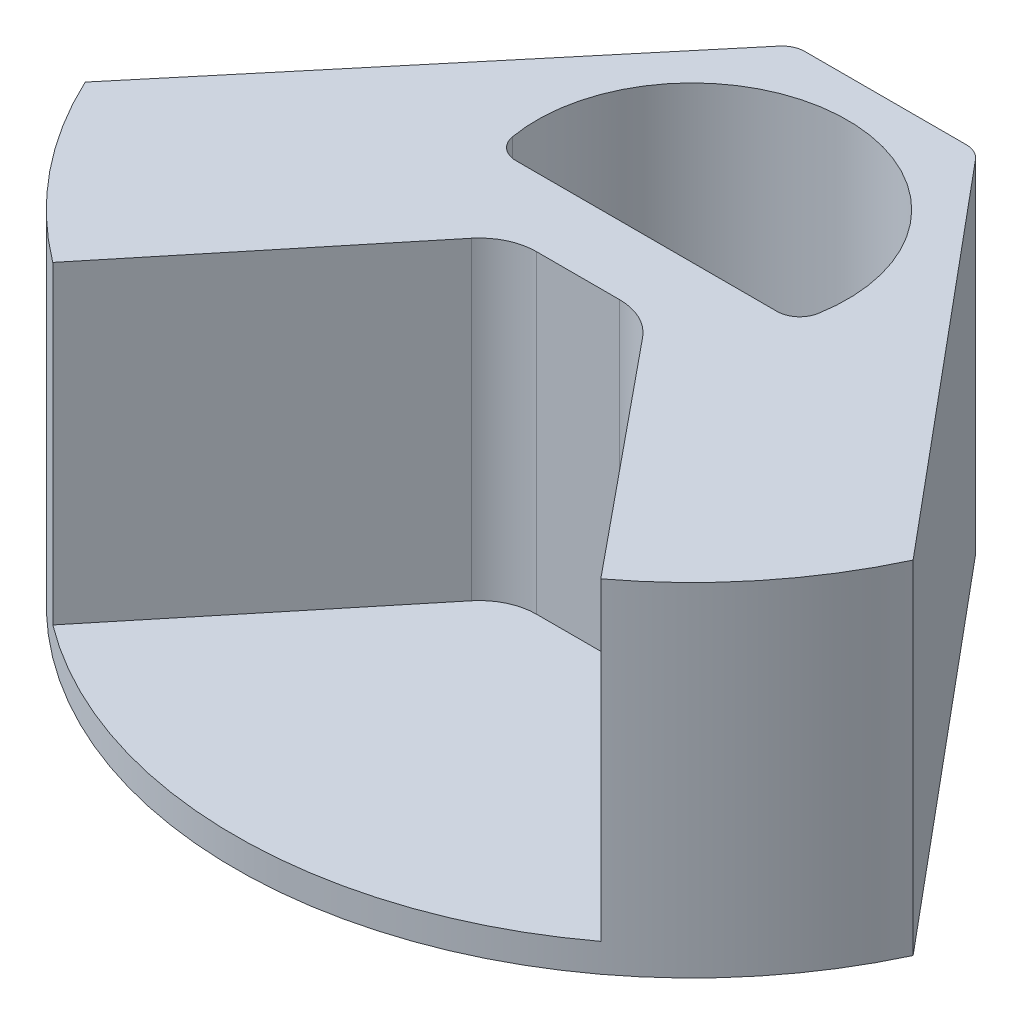
SolidWorks part; units mm, degrees
ref_plane "Front Plane" through (0, 0, 0) normal (0, 0, 1) x (1, 0, 0)
ref_plane "Top Plane" through (0, 0, 0) normal (0, 1, 0) x (1, 0, 0)
ref_plane "Right Plane" through (0, 0, 0) normal (1, 0, 0) x (0, 0, -1)
sketch "Sketch1" plane through (0, 0, 0) normal (0, 1, 0) x (1, 0, 0)
  circle A0 centre (0, 0) radius 50.8
  dimension "D1" = 101.6
extrude "Boss-Extrude1" add sketch "Sketch1" along normal blind 38.1
sketch "Sketch2" plane through (0, 38.1, 0) normal (0, 1, 0) x (1, 0, 0)
  line L0 (30.48, -40.64) -> (7.62, -12.7)
  line L1 (-7.62, -12.7) -> (7.62, -12.7)
  line L2 (-30.48, -40.64) -> (-30.48, -50.8)
  line L3 (-30.48, -50.8) -> (30.48, -50.8)
  line L4 (30.48, -40.64) -> (30.48, -50.8)
  line L5 (0, -20.955) -> (0, 20.955) construction
  line L6 (-30.48, -40.64) -> (-7.62, -12.7)
  circle A1 centre (0, 0) radius 50.8 construction
  dimension "D1" = 12.7
  dimension "D2" = 30.48
  dimension "D3" = 7.62
extrude "Cut-Extrude1" cut sketch "Sketch2" against normal offset from surface (34.925 mm away) 3.175 up to face at (0, 0, 50.8)
fillet "Fillet1" radius 6.35 2 edges at (7.62, 20.6375, 12.7) (-7.62, 20.6375, 12.7)
hole_wizard "M4 Clearance Hole1" positions "Sketch4" profile "Sketch5" hole size "M4" standard "ANSI Metric" end condition through all
sketch "Sketch4" plane through (0, 38.1, 0) normal (0, 1, 0) x (1, 0, 0)
  point P0 (0, 0)
sketch "Sketch5" plane through (0, 38.1, 0) normal (1, 0, 0) x (0, 0, 1)
  line L0 (0, 0) -> (0, 38.1)
  line L1 (0, 38.1) -> (2.475, 38.1)
  line L2 (2.475, 38.1) -> (2.475, 0)
  line L5 (2.475, 0) -> (0, 0)
  line L11 (0, -6.35) -> (0, 107.95) construction
  dimension "Thru Hole Dia." = 4.95
  dimension "Thru Hole Depth" = 38.1
sketch "Sketch8" plane through (0, 0, 0) normal (0, -1, 0) x (1, 0, 0)
  circle A0 centre (0, 0) radius 50.8
ref_axis "Axis1" through (0, 0, 0) along (0, 1, 0)
sketch "Sketch6" plane through (0, 38.1, 0) normal (0, 1, 0) x (1, 0, 0)
  line L1 (-46.0213, 56.4153) -> (46.0213, 56.4153)
  line L2 (-46.0213, 56.4153) -> (-46.0213, 21.51)
  line L3 (-46.0213, 21.51) -> (46.0213, 21.51)
  line L4 (46.0213, 56.4153) -> (46.0213, 21.51)
  arc A0 (30.48, -40.64) -> (-30.48, -40.64) centre (0, 0) ccw construction
  point P4 (0, 0)
  point P8 (0, 0)
extrude "Cut-Extrude2" cut sketch "Sketch6" against normal up to next
sketch "Sketch10" plane through (0, 38.1, 0) normal (0, 1, 0) x (1, 0, 0)
  line L1 (-46.0213, 21.51) -> (46.0213, 21.51) construction
  line L2 (-46.0213, 21.51) -> (-10.16, 21.51)
  line L7 (-10.16, 21.51) -> (-46.0434, -21.4627)
  line L8 (10.16, 21.51) -> (46.0434, -21.4627)
  line L9 (-9.5255, -15.0289) -> (-30.48, -40.64) construction
  line L10 (10.16, 21.51) -> (46.0213, 21.51)
  circle A5 centre (0, 0) radius 50.8 construction
  arc A6 (-46.0434, -21.4627) -> (-46.0213, 21.51) centre (-71.7905, 0.0368) cw
  arc A7 (46.0434, -21.4627) -> (46.0213, 21.51) centre (71.7905, 0.0368) ccw
  dimension "D1" = 20.32
  dimension "D2" = 0.573
extrude "Cut-Extrude3" cut sketch "Sketch10" against normal up to next
fillet "Fillet2" radius 2.54 2 edges at (10.16, 19.05, -21.51) (-10.16, 19.05, -21.51)
sketch "Sketch11" plane through (0, 38.1, 0) normal (0, 1, 0) x (1, 0, 0)
  line L0 (-16.508, -5.08) -> (16.508, -5.08)
  circle A0 centre (0, 0) radius 1.7
  arc A1 (16.508, -5.08) -> (-16.508, -5.08) centre (0, 0) ccw
  dimension "D1" = 34.544
  dimension "D2" = 5.08
extrude "Cut-Extrude4" cut sketch "Sketch11" against normal offset from surface (31.75 mm away) 6.35 up to face at (0, 0, 2.475)
fillet "Fillet3" radius 2.54 2 edges at (16.508, 22.225, 5.08) (-16.508, 22.225, 5.08)
sketch "Sketch12" plane through (0, 38.1, 0) normal (0, 1, 0) x (1, 0, 0)
  line L0 (-20.32, -28.2222) -> (20.32, -28.2222) construction
  line L1 (-9.5255, -15.0289) -> (-30.48, -40.64) construction
  line L2 (30.48, -40.64) -> (9.5255, -15.0289) construction
  dimension "D1" = 40.64
